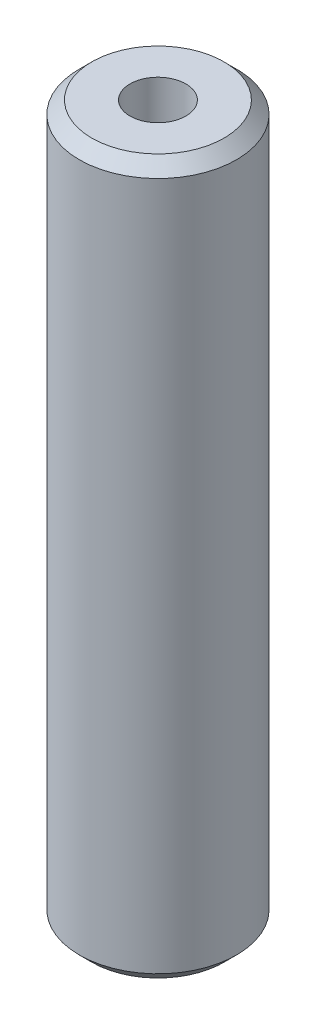
SolidWorks part; units mm, degrees
ref_plane "Front Plane" through (0, 0, 0) normal (0, 0, 1) x (1, 0, 0)
ref_plane "Top Plane" through (0, 0, 0) normal (0, 1, 0) x (1, 0, 0)
ref_plane "Right Plane" through (0, 0, 0) normal (1, 0, 0) x (0, 0, -1)
sketch "Sketch1" plane through (0, 0, 0) normal (0, 1, 0) x (1, 0, 0)
  circle A0 centre (0, 0) radius 30
  dimension "SHAFT_OD" = 60
extrude "Boss-Extrude1" add sketch "Sketch1" along normal blind 272.4186
sketch "Sketch2" plane through (0, 0, 0) normal (0, 1, 0) x (1, 0, 0)
  circle A0 centre (0, 0) radius 10.6557
  dimension "BORE_D" = 21.3114
extrude "Cut-Extrude1" cut sketch "Sketch2" along normal through all
chamfer "Chamfer1" distance 4.7644 angle 45 2 edges at (0, 272.4186, 30) (0, 0, 30)
